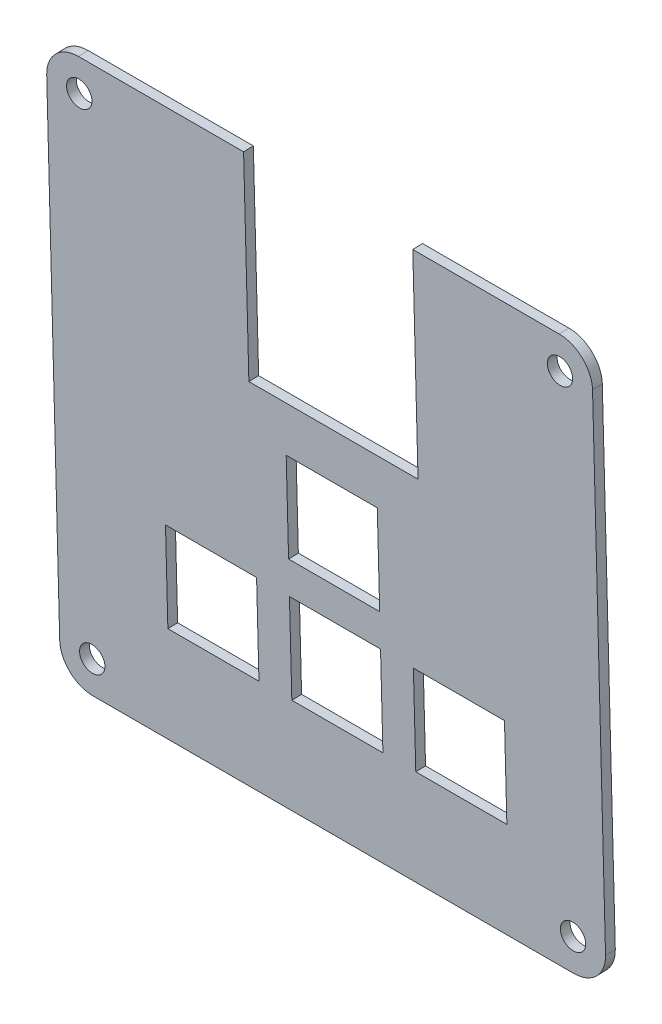
SolidWorks part; units mm, degrees
ref_plane "Front Plane" through (0, 0, 0) normal (0, 0, 1) x (1, 0, 0)
ref_plane "Top Plane" through (0, 0, 0) normal (0, 1, 0) x (1, 0, 0)
ref_plane "Right Plane" through (0, 0, 0) normal (1, 0, 0) x (0, 0, -1)
sketch "Sketch1" plane through (0, 0, 0) normal (0, 1, 0) x (1, 0, 0)
  line L0 (-6.7208, 16.4146) -> (6.2792, 16.4146)
  line L1 (-6.7208, 2.4146) -> (6.2792, 2.4146)
  line L2 (-7.2208, 15.9146) -> (-7.2208, 2.9146)
  line L3 (6.7792, 15.9146) -> (6.7792, 2.9146)
  line L4 (-25.7708, -2.6354) -> (-12.7708, -2.6354)
  line L5 (-25.7708, -16.6354) -> (-12.7708, -16.6354)
  line L6 (-26.2708, -3.1354) -> (-26.2708, -16.1354)
  line L7 (-12.2708, -3.1354) -> (-12.2708, -16.1354)
  line L8 (-6.7208, -2.6354) -> (6.2792, -2.6354)
  line L9 (-6.7208, -16.6354) -> (6.2792, -16.6354)
  line L10 (-7.2208, -3.1354) -> (-7.2208, -16.1354)
  line L11 (6.7792, -3.1354) -> (6.7792, -16.1354)
  line L12 (12.3292, -2.6354) -> (25.3292, -2.6354)
  line L13 (12.3292, -16.6354) -> (25.3292, -16.6354)
  line L14 (11.8292, -3.1354) -> (11.8292, -16.1354)
  line L15 (25.8292, -3.1354) -> (25.8292, -16.1354)
  arc A0 (-6.7208, 16.4146) -> (-7.2208, 15.9146) centre (-6.7208, 15.9146) ccw
  arc A1 (6.7792, 15.9146) -> (6.2792, 16.4146) centre (6.2792, 15.9146) ccw
  arc A2 (-7.2208, 2.9146) -> (-6.7208, 2.4146) centre (-6.7208, 2.9146) ccw
  arc A3 (6.2792, 2.4146) -> (6.7792, 2.9146) centre (6.2792, 2.9146) ccw
  arc A4 (-25.7708, -2.6354) -> (-26.2708, -3.1354) centre (-25.7708, -3.1354) ccw
  arc A5 (-12.2708, -3.1354) -> (-12.7708, -2.6354) centre (-12.7708, -3.1354) ccw
  arc A6 (-26.2708, -16.1354) -> (-25.7708, -16.6354) centre (-25.7708, -16.1354) ccw
  arc A7 (-12.7708, -16.6354) -> (-12.2708, -16.1354) centre (-12.7708, -16.1354) ccw
  arc A8 (-6.7208, -2.6354) -> (-7.2208, -3.1354) centre (-6.7208, -3.1354) ccw
  arc A9 (6.7792, -3.1354) -> (6.2792, -2.6354) centre (6.2792, -3.1354) ccw
  arc A10 (-7.2208, -16.1354) -> (-6.7208, -16.6354) centre (-6.7208, -16.1354) ccw
  arc A11 (6.2792, -16.6354) -> (6.7792, -16.1354) centre (6.2792, -16.1354) ccw
  arc A12 (12.3292, -2.6354) -> (11.8292, -3.1354) centre (12.3292, -3.1354) ccw
  arc A13 (25.8292, -3.1354) -> (25.3292, -2.6354) centre (25.3292, -3.1354) ccw
  arc A14 (11.8292, -16.1354) -> (12.3292, -16.6354) centre (12.3292, -16.1354) ccw
  arc A15 (25.3292, -16.6354) -> (25.8292, -16.1354) centre (25.3292, -16.1354) ccw
  dimension "D7" = 25.8292
  dimension "D1" = 2.4146
  dimension "D2" = 5.05
  dimension "D3" = 5.05
  dimension "D4" = 5.05
  dimension "D5" = 14
  dimension "D6" = 14
sketch "Sketch2" plane through (0, 0, 0) normal (0, 1, 0) x (1, 0, 0)
  line L1 (43.1982, 55.2236) -> (-40.6918, 55.2236)
  line L2 (43.1982, 55.2236) -> (43.1982, -31.0564)
  line L3 (43.1982, -31.0564) -> (-40.6918, -31.0564)
  line L4 (-40.6918, 55.2236) -> (-40.6918, -31.0564)
  line L5 (43.1982, 55.2236) -> (-40.6918, -31.0564) construction
  line L6 (43.1982, -31.0564) -> (-40.6918, 55.2236) construction
  line L12 (-25.7708, -16.6354) -> (-12.7708, -16.6354) construction
  line L13 (-26.2708, -3.1354) -> (-26.2708, -16.1354) construction
  line L16 (-13.1918, 55.2236) -> (12.8082, 55.2236)
  line L17 (-13.1918, 55.2236) -> (-13.1918, 24.2236)
  line L18 (-13.1918, 24.2236) -> (12.8082, 24.2236)
  line L19 (12.8082, 55.2236) -> (12.8082, 24.2236)
  circle A0 centre (38.1982, 50.2236) radius 1.95
  circle A1 centre (-35.6918, 50.2236) radius 1.95
  circle A2 centre (-35.6918, -26.0564) radius 1.95
  circle A3 centre (38.1982, -26.0564) radius 1.95
  point P0 (0, 0)
  dimension "D8" = 3.9
  dimension "D9" = 3.9
  dimension "D10" = 3.9
  dimension "D11" = 3.9
  dimension "D1" = 83.89
  dimension "D2" = 86.28
  dimension "D3" = 14.421
  dimension "D4" = 14.421
  dimension "D5" = 26
  dimension "D6" = 31
  dimension "D7" = 27.5
  dimension "D12" = 5
  dimension "D13" = 5
  dimension "D14" = 5
  dimension "D15" = 5
  dimension "D16" = 5
  dimension "D17" = 5
  dimension "D18" = 5
  dimension "D19" = 5
extrude "Boss-Extrude3" add sketch "Sketch2" along normal blind 1.5 contours L1 L19 L18 L17 L4 L3 L2 A3 A2 A1 A0 region at (1.4356, 0, -8.5941)
extrude "Cut-Extrude5" [suppressed] cut sketch "Sketch1" against normal blind 4.5 and the other way blind 7
fillet "Fillet4" radius 5 4 edges at (-40.6918, 0.75, 31.0564) (43.1982, 0.75, 31.0564) (43.1982, 0.75, -55.2236) (-40.6918, 0.75, -55.2236)
move or copy body "Body-Move/Copy1" bodies to move or copy 103 copy no rotation origin (0, 0.75, -12.2836) rotation axis (-1, 0, 0) rotation angle 91.5
move or copy body "Body-Move/Copy2" bodies to move or copy 106 copy no rotation origin (0.4032, 0.75, 0) rotation axis (0, 0, 1) rotation angle 180
sketch "Sketch3" plane through (0, 0.3416, -13.0445) normal (0, 0.0262, -0.9997) x (-1, 0, 0)
  line L0 (-41.4982, 38.3682) -> (-41.4982, -37.9118) construction
  line L1 (-26.5982, -13.8118) -> (-12.5982, -13.8118)
  line L2 (-26.5982, -13.8118) -> (-26.5982, -27.8118)
  line L3 (-26.5982, -27.8118) -> (-12.5982, -27.8118)
  line L4 (-12.5982, -13.8118) -> (-12.5982, -27.8118)
  line L5 (-7.5482, -13.8118) -> (6.4518, -13.8118)
  line L6 (-7.5482, -13.8118) -> (-7.5482, -27.8118)
  line L7 (-7.5482, -27.8118) -> (6.4518, -27.8118)
  line L8 (6.4518, -13.8118) -> (6.4518, -27.8118)
  line L9 (11.5018, -13.8118) -> (25.5018, -13.8118)
  line L10 (11.5018, -13.8118) -> (11.5018, -27.8118)
  line L11 (11.5018, -27.8118) -> (25.5018, -27.8118)
  line L12 (25.5018, -13.8118) -> (25.5018, -27.8118)
  line L13 (-7.5482, 5.2382) -> (6.4518, 5.2382)
  line L14 (-7.5482, 5.2382) -> (-7.5482, -8.7618)
  line L15 (-7.5482, -8.7618) -> (6.4518, -8.7618)
  line L16 (6.4518, 5.2382) -> (6.4518, -8.7618)
  line L17 (37.3918, -42.9118) -> (-36.4982, -42.9118) construction
  dimension "D1" = 14
  dimension "D2" = 14
  dimension "D3" = 14
  dimension "D4" = 14
  dimension "D5" = 14
  dimension "D6" = 14
  dimension "D7" = 14
  dimension "D8" = 14
  dimension "D9" = 5.05
  dimension "D10" = 5.05
  dimension "D11" = 5.05
  dimension "D12" = 5.05
  dimension "D13" = 5.05
  dimension "D14" = 5.05
  dimension "D15" = 14.9
  dimension "D16" = 15.1
extrude "Cut-Extrude6" cut sketch "Sketch3" against normal blind 10
